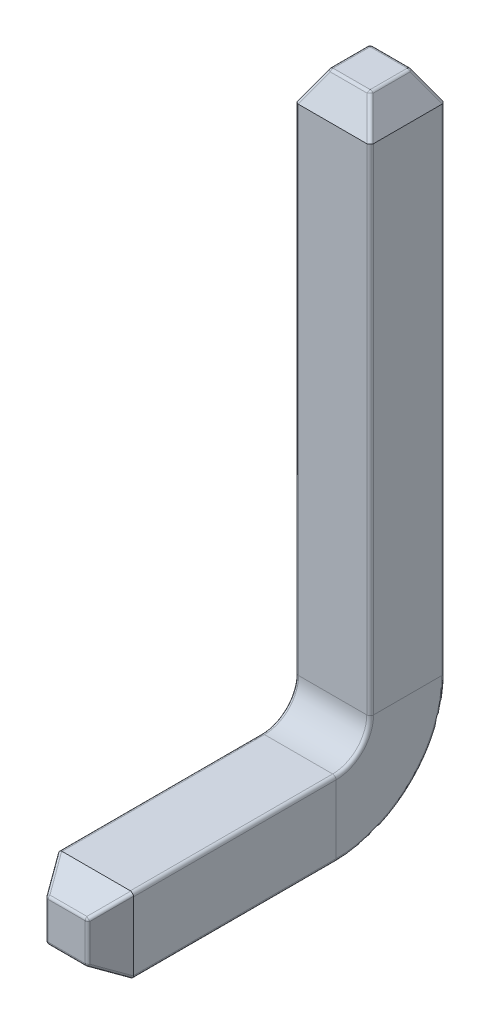
SolidWorks part; units mm, degrees
note: The reader was unsure of these and kept them because the rebuilt part matched: flange length of "边线-法兰1".
ref_plane "前视基准面" through (0, 0, 0) normal (0, 0, 1) x (1, 0, 0)
ref_plane "上视基准面" through (0, 0, 0) normal (0, 1, 0) x (1, 0, 0)
ref_plane "右视基准面" through (0, 0, 0) normal (1, 0, 0) x (0, 0, -1)
sketch "Sketch2" plane through (0, 0, 0) normal (0, 0, 1) x (1, 0, 0)
  line L1 (-0.22, 1.8575) -> (0.22, 1.8575)
  line L2 (-0.22, 1.8575) -> (-0.22, -1.8575)
  line L3 (-0.22, -1.8575) -> (0.22, -1.8575)
  line L4 (0.22, 1.8575) -> (0.22, -1.8575)
  line L5 (-0.22, 1.8575) -> (0.22, -1.8575) construction
  line L6 (-0.22, -1.8575) -> (0.22, 1.8575) construction
  point P0 (0, 0)
  dimension "D1" = 0.44
  dimension "D2" = 3.715
base flange "Base-Flange1" sketch "Sketch2" thickness 0.44 reverse thickness direction no parameters "D1"=0.7366
edge flange "边线-法兰1" sketch "Sketch15" flange angle 90 flange length 2 flange position material inside bend radius 0.2 thickness 0.44 relief rectangular parameters "D6"=10
sketch "Sketch15" plane through (0, -1.8575, 0) normal (0, -1, 0) x (1, 0, 0)
  line L0 (-0.22, 0) -> (0.22, 0) construction
  line L1 (-0.22, 0) -> (0.22, 0)
  line L2 (-0.22, 0) -> (-0.22, 1.56)
  line L3 (-0.22, 1.56) -> (0.22, 1.56)
  line L4 (0.22, 1.56) -> (0.22, 0)
bend "边线折弯1" bend radius 0.2 bend angle 90 parameters "D5"=1
chamfer "Chamfer2" distance 0.1 angle 60 4 edges at (-0.22, 1.8575, -0.22) (0, 1.8575, -0.44) (0.22, 1.8575, -0.22) (0, 1.8575, 0) first distance on face at (0, 1.8575, -0.22)
chamfer "Chamfer3" distance 0.1 angle 60 4 edges at (0.22, -1.6375, 1.56) (0, -1.8575, 1.56) (-0.22, -1.6375, 1.56) (0, -1.4175, 1.56) first distance on face at (0, -1.6375, 1.56)
fillet "Fillet1" radius 0.02 28 edges at (0.22, 0.2334, 0) (0.22, 0.2334, -0.44) (-0.22, -1.67, -0.2525) (0.22, -1.67, -0.2525) (-0.22, -1.3589, 0.0586) (0.22, -1.3589, 0.0586) (0.22, -1.4175, 0.7934) (0.22, -1.8575, 0.7934) (0, 1.8575, -0.1) (0.12, 1.8575, -0.22) (0, 1.8575, -0.34) (-0.12, 1.8575, -0.22) (-0.22, 0.2334, 0) (-0.22, 0.2334, -0.44) (0.17, 1.7709, -0.39) (0.17, 1.7709, -0.05) (-0.17, 1.7709, -0.39) (-0.17, 1.7709, -0.05) (0, -1.5175, 1.56) (-0.12, -1.6375, 1.56) (0, -1.7575, 1.56) (0.12, -1.6375, 1.56) (-0.22, -1.8575, 0.7934) (-0.22, -1.4175, 0.7934) (-0.17, -1.8075, 1.4734) (-0.17, -1.4675, 1.4734) (0.17, -1.8075, 1.4734) (0.17, -1.4675, 1.4734)
sketch "折弯-线1" plane through (0, 0, 0) normal (0, 1, 0) x (1, 0, 0)
sketch "边界框1" plane through (0, 0, 0) normal (0, 1, 0) x (1, 0, 0)
sheet metal parameters "钣金6" thickness 0.44 parameters "D1"=0.7366
flat pattern "平板型式6" [suppressed]
sketch "折弯-线2" plane through (0, 0, 0) normal (0, 1, 0) x (1, 0, 0)
sketch "边界框2" [suppressed] plane through (0, 0, 0) normal (0, 1, 0) x (1, 0, 0)
sheet metal parameters "钣金7" thickness 0.44 parameters "D1"=0.7366
flat pattern "平板型式6" [suppressed]
sketch "折弯-线2" plane through (0, 0, 0) normal (0, 1, 0) x (1, 0, 0)
sketch "边界框2" [suppressed] plane through (0, 0, 0) normal (0, 1, 0) x (1, 0, 0)
bend of the flat pattern "展平-<边线折弯1>1"
